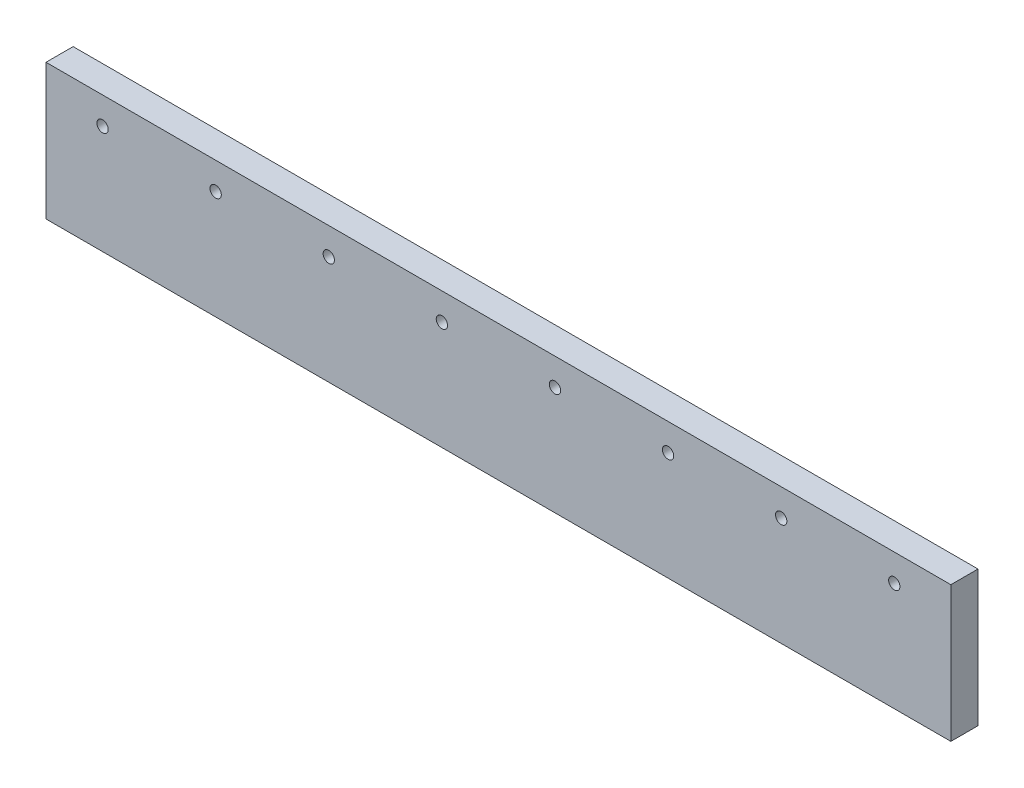
SolidWorks part; units mm, degrees
ref_plane "Front" through (0, 0, 0) normal (0, 0, 1) x (1, 0, 0)
ref_plane "Top" through (0, 0, 0) normal (0, 1, 0) x (1, 0, 0)
ref_plane "Right" through (0, 0, 0) normal (1, 0, 0) x (0, 0, -1)
sketch "Esquisse1" plane through (0, 0, 0) normal (0, 0, 1) x (1, 0, 0)
  line L1 (0, 0) -> (200, 0)
  line L2 (0, 0) -> (0, 30)
  line L3 (0, 30) -> (200, 30)
  line L4 (200, 0) -> (200, 30)
  dimension "D1" = 30
  dimension "D2" = 200
extrude "Boss.-Extru.1" add sketch "Esquisse1" along normal blind 6
sketch "Esquisse2" plane through (0, 0, 6) normal (0, 0, 1) x (1, 0, 0)
  line L0 (0, 24) -> (200, 24) construction
  line L1 (0, 30) -> (0, 0) construction
  line L2 (200, 0) -> (200, 30) construction
  line L3 (200, 30) -> (0, 30) construction
  line L4 (12.5, 24) -> (37.5, 24) construction
  circle A0 centre (12.5, 24) radius 1.25
  circle A1 centre (37.5, 24) radius 1.25
  circle A2 centre (62.5, 24) radius 1.25
  circle A3 centre (87.5, 24) radius 1.25
  circle A4 centre (112.5, 24) radius 1.25
  circle A5 centre (137.5, 24) radius 1.25
  circle A6 centre (162.5, 24) radius 1.25
  circle A7 centre (187.5, 24) radius 1.25
  point P11 (37.3032, 30.8693)
  dimension "D1" = 12.5
  dimension "D2" = 2.5
  dimension "D3" = 6
  dimension "D5" = 25
  dimension "D4" = 8
extrude "Enlèv. mat.-Extru.1" cut sketch "Esquisse2" against normal up to vertex (6 mm away) up to point (200, 30, 0)
